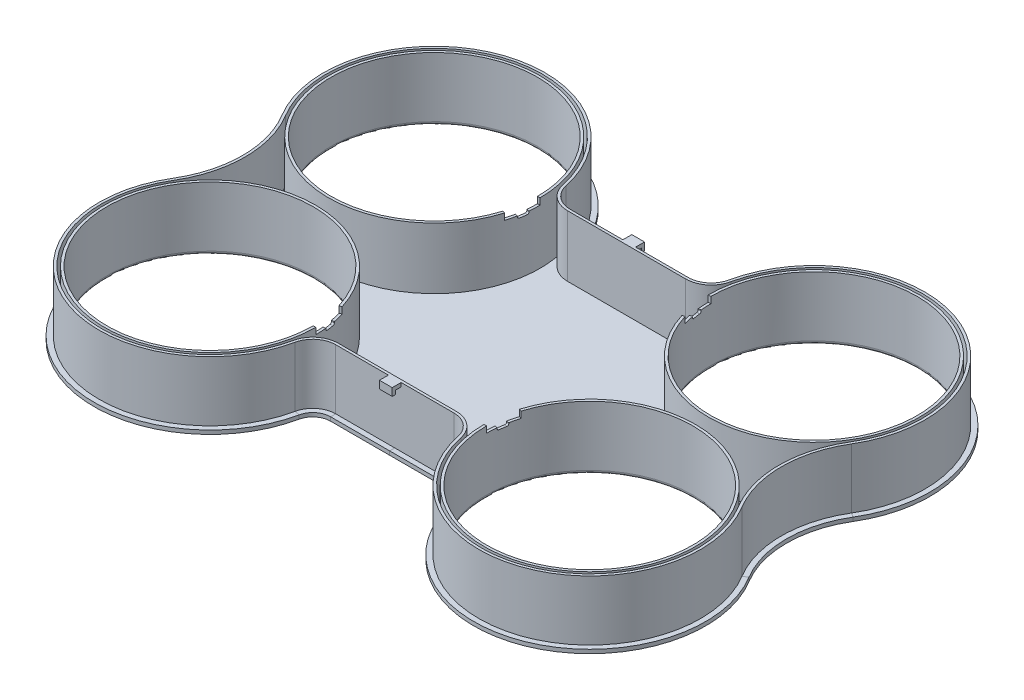
SolidWorks part; units mm, degrees
material "P-Filament 721"
ref_plane "Front Plane" through (0, 0, 0) normal (0, 0, 1) x (1, 0, 0)
ref_plane "Top Plane" through (0, 0, 0) normal (0, 1, 0) x (1, 0, 0)
ref_plane "Right Plane" through (0, 0, 0) normal (1, 0, 0) x (0, 0, -1)
sketch "Sketch1" plane through (0, 0, 0) normal (0, 1, 0) x (1, 0, 0)
  line L0 (-1720.3603, 0) -> (84297.6564, 0) construction
  line L1 (0, -1720.3603) -> (0, 84297.6564) construction
  line L2 (-23.1653, 46) -> (23.1653, 46)
  line L3 (-23.1653, -46) -> (23.1653, -46)
  arc A0 (111.7183, 21.4824) -> (31.9655, 53.1143) centre (74.5, 44) ccw
  circle A1 centre (74.5, 44) radius 40.5
  arc A2 (111.7183, 21.4824) -> (111.7183, -21.4824) centre (147.2255, 0) ccw
  arc A3 (23.1653, 46) -> (31.9655, 53.1143) centre (23.1653, 55) ccw
  arc A4 (23.1653, -46) -> (31.9655, -53.1143) centre (23.1653, -55) cw
  circle A5 centre (74.5, -44) radius 40.5
  arc A6 (111.7183, -21.4824) -> (31.9655, -53.1143) centre (74.5, -44) cw
  arc A7 (-111.7183, -21.4824) -> (-31.9655, -53.1143) centre (-74.5, -44) ccw
  circle A8 centre (-74.5, -44) radius 40.5
  arc A9 (-23.1653, -46) -> (-31.9655, -53.1143) centre (-23.1653, -55) ccw
  arc A10 (-23.1653, 46) -> (-31.9655, 53.1143) centre (-23.1653, 55) cw
  arc A11 (-111.7183, 21.4824) -> (-111.7183, -21.4824) centre (-147.2255, 0) cw
  circle A12 centre (-74.5, 44) radius 40.5
  arc A13 (-111.7183, 21.4824) -> (-31.9655, 53.1143) centre (-74.5, 44) cw
  point P19 (0, 46)
  point P33 (0, -46)
  dimension "43.5*2" = 87
  dimension "D2" = 3
  dimension "D3" = 83
  dimension "D4" = 9
  dimension "D6" = 175
  dimension "D7" = 236
  dimension "D5" = 46
extrude "Boss-Extrude1" add sketch "Sketch1" along normal blind 25
shell "Shell1" thickness 1 removed face at (0, 25, 0)
fillet "Fillet1" radius 1.5 4 edges at (74.5, 0, -3.5) (74.5, 0, 3.5) (-74.5, 0, 84.5) (-74.5, 0, -84.5)
sketch "Sketch2" plane through (0, 0, 0) normal (1, 0, 0) x (0, 0, -1)
  line L1 (-46, 0) -> (-48, 0)
  line L2 (-46, 0) -> (-46, 1.5)
  line L3 (-46, 1.5) -> (-48, 1.5)
  line L4 (-48, 0) -> (-48, 1.5)
  dimension "D1" = 46
  dimension "D2" = 1.5
  dimension "D3" = 2
sweep "Lip" add profiles "Sketch2" path "Sketch1<2>"
sketch "Sketch1<2>" plane through (0, 0, 0) normal (0, 1, 0) x (1, 0, 0) same geometry as "Sketch1"
sketch "Sketch3" plane through (0, 25, 0) normal (0, 1, 0) x (1, 0, 0)
  line L0 (-1000, 0) -> (49000, 0) construction
  line L1 (0, -1000) -> (0, 49000) construction
  line L2 (74.5, -44) -> (34.8134, -31.8666)
  line L3 (74.5, -44) -> (33, -44)
  line L4 (-39.9523, -65.1355) -> (-47.6413, -13.6873) construction
  line L5 (-74.5, -44) -> (-33, -44)
  line L6 (-74.5, -44) -> (-34.8134, -31.8666)
  line L7 (74.5, -44) -> (34.8134, -31.8666)
  line L8 (74.5, -44) -> (33, -44)
  line L9 (-74.5, -44) -> (-33, -44)
  line L10 (-74.5, -44) -> (-34.8134, -31.8666)
  line L11 (-74.5, 44) -> (-34.8134, 31.8666)
  line L12 (-74.5, 44) -> (-33, 44)
  line L13 (74.5, 44) -> (33, 44)
  line L14 (74.5, 44) -> (34.8134, 31.8666)
  line L15 (-74.5, 44) -> (-34.8134, 31.8666)
  line L16 (-74.5, 44) -> (-33, 44)
  line L17 (74.5, 44) -> (33, 44)
  line L18 (74.5, 44) -> (34.8134, 31.8666)
  line L19 (-33, -44) -> (-34.8134, -31.8666) construction
  circle A0 centre (74.5, -44) radius 41.5 construction
  circle A1 centre (74.5, -44) radius 40.5 construction
  arc A2 (34.8134, -31.8666) -> (33, -44) centre (74.5, -44) ccw
  arc A3 (-34.8134, -31.8666) -> (-33, -44) centre (-74.5, -44) cw
  arc A4 (34.8134, -31.8666) -> (33, -44) centre (74.5, -44) ccw
  arc A5 (-34.8134, -31.8666) -> (-33, -44) centre (-74.5, -44) cw
  arc A6 (-34.8134, 31.8666) -> (-33, 44) centre (-74.5, 44) ccw
  arc A7 (34.8134, 31.8666) -> (33, 44) centre (74.5, 44) cw
  arc A8 (-34.8134, 31.8666) -> (-33, 44) centre (-74.5, 44) ccw
  arc A9 (34.8134, 31.8666) -> (33, 44) centre (74.5, 44) cw
  circle A11 centre (-74.5, -44) radius 40.5 construction
  dimension "D1" = 17
  dimension "D2" = 10
extrude "ArmCutsMain" cut sketch "Sketch3" against normal blind 2.5 contours A3 L6 L5 | L2 A2 L3 | L11 A6 L12 | A7 L14 L13 region at (47.2375, 25, 39.9256) region at (-47.2375, 25, 39.9256) region at (-47.2375, 25, -39.9256) region at (47.2375, 25, -39.9256)
ref_plane "ArmCutDetailPlane" through (39.6894, 0, 5.9316) normal (-0.989, 0, -0.1478) x (-0.1478, 0, 0.989)
sketch "Sketch6" plane through (39.6894, 0, 5.9316) normal (-0.989, 0, -0.1478) x (-0.1478, 0, 0.989)
  line L1 (34.5186, 22.5) -> (30.5186, 22.5)
  line L2 (34.5186, 22.5) -> (34.5186, 22.1)
  line L3 (33.9186, 21.5) -> (31.1186, 21.5)
  line L4 (30.5186, 22.5) -> (30.5186, 22.1)
  line L5 (38.639, 22.5) -> (26.3708, 22.5) construction
  line L6 (26.5186, 22.5) -> (26.5186, 25) construction
  arc A0 (34.5186, 22.1) -> (33.9186, 21.5) centre (33.9186, 22.1) cw
  arc A1 (31.1186, 21.5) -> (30.5186, 22.1) centre (31.1186, 22.1) cw
  point P6 (32.5186, 22.5)
  point P11 (34.5186, 21.5)
  point P14 (30.5186, 21.5)
  dimension "D3" = 0.6
  dimension "D1" = 6
  dimension "D2" = 4
  dimension "D4" = 1
extrude "ArmCutDetail" cut sketch "Sketch6" along normal blind 5
mirror "ArmCutDupes" about plane through (0, 0, 0) normal (1, 0, 0) of "ArmCutDetail" second plane through (0, 0, 0) second plane normal (0, 0, 1)
sketch "Sketch7" plane through (0, 0, 0) normal (1, 0, 0) x (0, 0, -1)
  line L0 (46, 25) -> (49.5, 25)
  line L1 (49.5, 25) -> (49.5, 22)
  line L2 (49.5, 22) -> (48.25, 22)
  line L3 (48.25, 22) -> (48.25, 23.5)
  line L4 (48.25, 23.5) -> (46, 23.5)
  line L5 (46, 23.5) -> (46, 25)
  line L6 (46, 25) -> (46, 1.5) construction
  line L7 (-45, 25) -> (-52.9048, 25) construction
  line L8 (0, -1000) -> (0, 49000) construction
  line L9 (-46, 23.5) -> (-46, 25)
  line L10 (-48.25, 23.5) -> (-46, 23.5)
  line L11 (-48.25, 22) -> (-48.25, 23.5)
  line L12 (-49.5, 22) -> (-48.25, 22)
  line L13 (-49.5, 25) -> (-49.5, 22)
  line L14 (-46, 25) -> (-49.5, 25)
  dimension "D1" = 3.5
  dimension "D2" = 2.25
  dimension "D3" = 3
  dimension "D4" = 1.5
extrude "Hooks" add sketch "Sketch7" along normal mid plane 5
